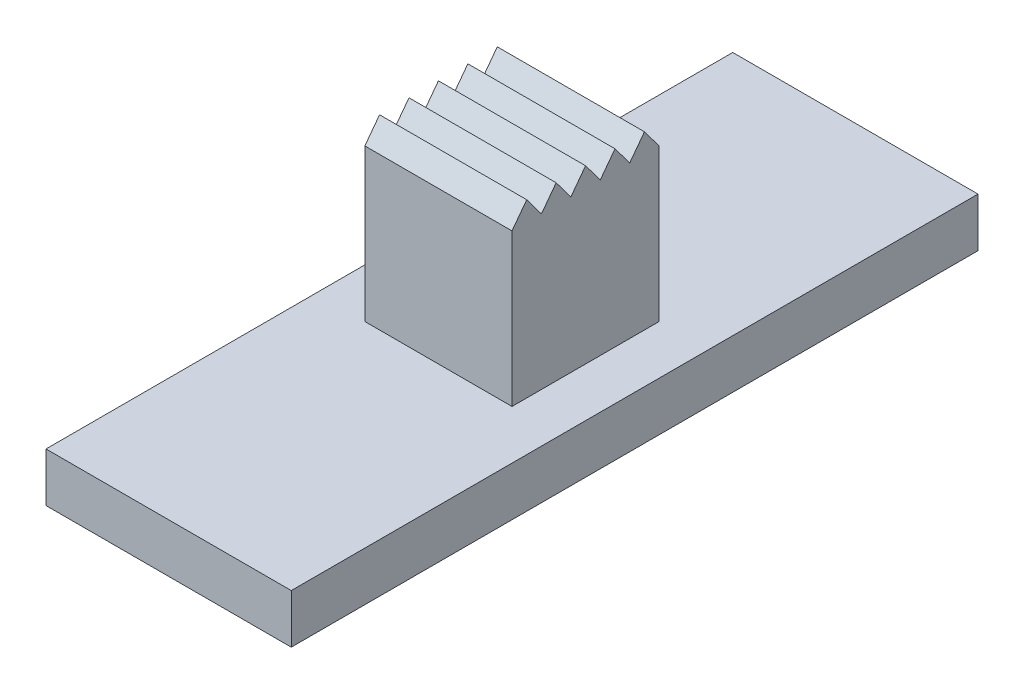
SolidWorks part; units mm, degrees
material "Nylon 101"
ref_plane "Plan de face" through (0, 0, 0) normal (0, 0, 1) x (1, 0, 0)
ref_plane "Plan de dessus" through (0, 0, 0) normal (0, 1, 0) x (1, 0, 0)
ref_plane "Plan de droite" through (0, 0, 0) normal (1, 0, 0) x (0, 0, -1)
sketch "Esquisse1" plane through (0, 0, 0) normal (1, 0, 0) x (0, 0, -1)
  line L0 (0, 6.325) -> (0, -5.475) construction
  line L1 (-7, 0) -> (-1.5, 0)
  line L2 (-1.5, 0) -> (-1.5, 3.1)
  line L3 (0.3, 3.1) -> (0, 3.5)
  line L4 (1.5, 3.1) -> (1.5, 0)
  line L5 (1.5, 0) -> (7, 0)
  line L6 (7, 0) -> (7, -1)
  line L7 (7, -1) -> (-7, -1)
  line L8 (-7, -1) -> (-7, 0)
  line L9 (-1.5, 3.1) -> (-1.2, 3.5)
  line L10 (-1.2, 3.5) -> (-0.9, 3.1)
  line L11 (-0.9, 3.1) -> (-0.6, 3.5)
  line L12 (-0.6, 3.5) -> (-0.3, 3.1)
  line L13 (-0.3, 3.1) -> (0, 3.5)
  line L14 (0.6, 3.5) -> (0.3, 3.1)
  line L15 (0.9, 3.1) -> (0.6, 3.5)
  line L16 (1.2, 3.5) -> (0.9, 3.1)
  line L17 (1.5, 3.1) -> (1.2, 3.5)
  dimension "D1" = 3.5
  dimension "D2" = 0.3
  dimension "D3" = 0.6
  dimension "D4" = 0.6
  dimension "D5" = 0.4
  dimension "D6" = 3
  dimension "D7" = 0.3
  dimension "D8" = 0.3
  dimension "D9" = 7
  dimension "D10" = 1
extrude "Boss.-Extru.1" add sketch "Esquisse1" along normal blind 1.5 and the other way blind 1.5
sketch "Esquisse2" plane through (1.5, 0, 0) normal (1, 0, 0) x (0, 0, -1)
  line L1 (-7, 0) -> (7, 0)
  line L2 (-7, 0) -> (-7, -1)
  line L3 (-7, -1) -> (7, -1)
  line L4 (7, 0) -> (7, -1)
extrude "Boss.-Extru.2" add sketch "Esquisse2" along normal blind 1
mirror "Symétrie1" about plane through (0, 0, 0) normal (1, 0, 0) of "Boss.-Extru.2"
